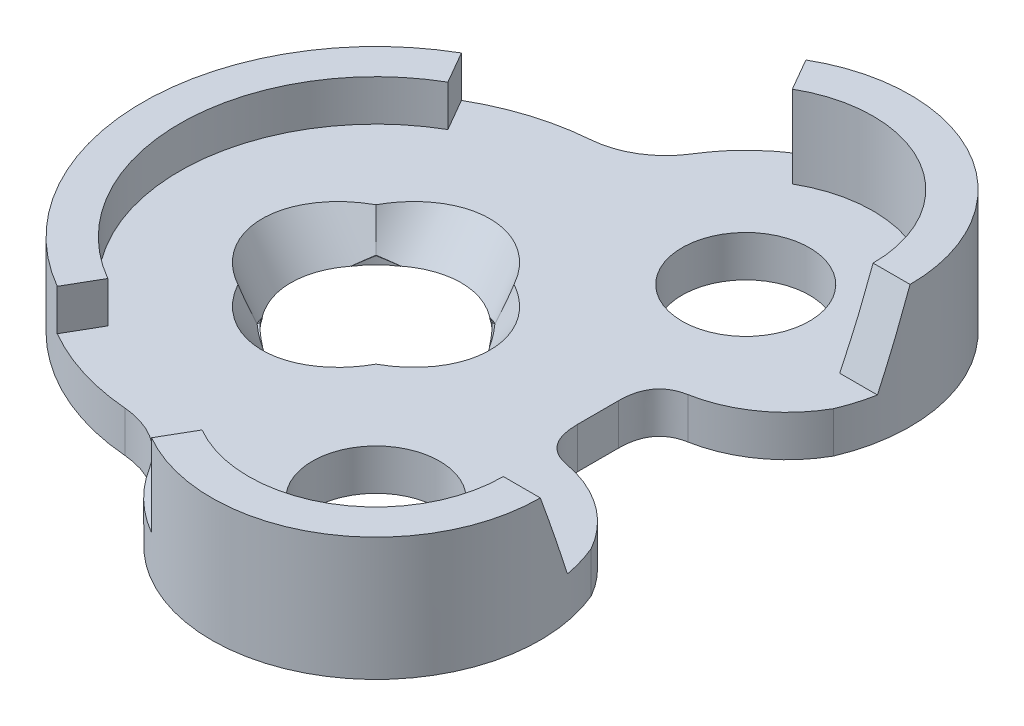
SolidWorks part; units mm, degrees
ref_plane "Front Plane" through (0, 0, 0) normal (0, 0, 1) x (1, 0, 0)
ref_plane "Top Plane" through (0, 0, 0) normal (0, 1, 0) x (1, 0, 0)
ref_plane "Right Plane" through (0, 0, 0) normal (1, 0, 0) x (0, 0, -1)
sketch "Sketch1" plane through (0, 0, 0) normal (0, 1, 0) x (1, 0, 0)
  circle A0 centre (-6.1056, 7.1668) radius 1.55
  circle A1 centre (2.8944, 7.1668) radius 1.55
  circle A3 centre (-6.1056, -1.8332) radius 1.55
  circle A4 centre (2.8944, -1.8332) radius 1.55
  arc A5 (-3.6359, 10.3133) -> (-9.2521, 4.6971) centre (-6.1056, 7.1668) ccw
  arc A6 (6.0409, 4.6971) -> (0.4247, 10.3133) centre (2.8944, 7.1668) ccw
  arc A7 (-9.2521, 0.6365) -> (-3.6359, -4.9797) centre (-6.1056, -1.8332) ccw
  arc A8 (0.224, -4.8113) -> (6.0409, 0.6365) centre (2.8944, -1.8332) ccw
  arc A9 (-9.2521, 0.6365) -> (-9.2521, 4.6971) centre (-11.4675, 2.6668) ccw
  arc A10 (-3.6359, 10.3133) -> (0.4247, 10.3133) centre (-1.6056, 12.5287) ccw
  arc A11 (6.0409, 4.6971) -> (6.0409, 0.6365) centre (8.2563, 2.6668) ccw
  arc A12 (0.224, -4.8113) -> (-3.6359, -4.9797) centre (-1.6056, -7.1951) ccw
  dimension "D3" = 7
  dimension "D5" = 6.01
  dimension "D6" = 6.01
  dimension "D11" = 6.01
  dimension "D14" = 6.01
  dimension "D17" = 4
  dimension "D18" = 4
  dimension "D19" = 4
  dimension "D20" = 4
  dimension "D21" = 3.1
  dimension "D22" = 3.1
  dimension "D23" = 3.1
  dimension "D24" = 3.1
  dimension "D1" = 9
  dimension "D2" = 9
  dimension "D4" = 7
  dimension "D7" = 7
  dimension "D8" = 7
  dimension "D9" = 7
  dimension "D10" = 7
  dimension "D12" = 7
  dimension "D13" = 7
  dimension "D15" = 9
  dimension "D16" = 0
extrude "Boss-Extrude1" add sketch "Sketch1" along normal blind 3
sketch "Sketch2" plane through (0, 3, 0) normal (0, 1, 0) x (1, 0, 0)
  arc A0 (-3.4925, 8.8346) -> (-7.7734, 4.5537) centre (-6.1056, 7.1668) ccw
  arc A1 (4.5622, 4.5537) -> (0.2812, 8.8346) centre (2.8944, 7.1668) ccw
  arc A2 (-7.7734, 0.78) -> (-3.4925, -3.501) centre (-6.1056, -1.8332) ccw
  arc A3 (0.2812, -3.501) -> (4.5622, 0.78) centre (2.8944, -1.8332) ccw
  arc A4 (0.2812, -3.501) -> (-3.4925, -3.501) centre (-1.6056, -4.0126) ccw
  arc A5 (-7.7734, 0.78) -> (-7.7734, 4.5537) centre (-8.2851, 2.6668) ccw
  arc A6 (4.5622, 4.5537) -> (4.5622, 0.78) centre (5.0738, 2.6668) ccw
  arc A7 (-3.4925, 8.8346) -> (0.2812, 8.8346) centre (-1.6056, 9.3463) ccw
  dimension "D1" = 5
  dimension "D9" = 3.91
  dimension "D10" = 3.91
  dimension "D11" = 3.91
  dimension "D12" = 3.91
  dimension "D13" = 3.1
  dimension "D14" = 3.1
  dimension "D15" = 3.1
  dimension "D16" = 3.1
  dimension "D2" = 5
  dimension "D3" = 5
  dimension "D4" = 5
  dimension "D5" = 5
  dimension "D6" = 5
  dimension "D7" = 5
  dimension "D8" = 5
extrude "Cut-Extrude1" cut sketch "Sketch2" against normal blind 2
ref_plane "Plane1" through (5.2513, 0, -2.6668) normal (1, 0, 0) x (0, 0, -1)
sketch "Sketch3" plane through (5.2513, 0, -2.6668) normal (1, 0, 0) x (0, 0, -1)
  line L1 (-2.95, 3) -> (2.95, 3)
  line L2 (-2.95, 3) -> (-2.95, 0)
  line L3 (-2.95, 0) -> (2.95, 0)
  line L4 (2.95, 3) -> (2.95, 0)
  line L5 (-8.5, 0) -> (-2.0303, 0) construction
  line L6 (-2.0303, 3) -> (-8.5, 3) construction
  dimension "D1" = 0
  dimension "D2" = 0
  dimension "D3" = 0
  dimension "D4" = 0
extrude "Boss-Extrude2" add sketch "Sketch3" along normal blind 8
sketch "Sketch4" plane through (0, 3, 0) normal (0, 1, 0) x (1, 0, 0)
  line L1 (0.4583, -1.8332) -> (14.1177, -1.8332)
  line L2 (0.4583, -1.8332) -> (0.4583, 7.1668)
  line L3 (0.4583, 7.1668) -> (14.1177, 7.1668)
  line L4 (14.1177, -1.8332) -> (14.1177, 7.1668)
  circle A0 centre (2.8944, -1.8332) radius 1.55 construction
  circle A1 centre (2.8944, 7.1668) radius 1.55 construction
  dimension "D1" = 0
  dimension "D2" = 0
extrude "Cut-Extrude2" cut sketch "Sketch4" against normal up to surface (2 mm away) draft 20
sketch "Sketch5" plane through (0, 1, 0) normal (0, 1, 0) x (1, 0, 0)
  line L11 (6.5819, -0.2832) -> (13.2513, -0.2832) construction
  circle A2 centre (10.3944, 2.7168) radius 0.75
  circle A5 centre (2.8944, 7.1668) radius 1.55 construction
  dimension "D1" = 7.5
  dimension "D2" = 3
extrude "Cut-Extrude3" cut sketch "Sketch5" against normal blind 1.3
sketch "Sketch6" plane through (0, 3, 0) normal (0, 1, 0) x (1, 0, 0)
  line L0 (-3.4925, -3.501) -> (-3.7025, -1.3276)
  line L1 (-3.7025, -1.3276) -> (0.3682, -0.9343)
  line L2 (0.3682, -0.9343) -> (0.2812, -3.501)
  arc A1 (-3.4925, -3.501) -> (0.2812, -3.501) centre (-1.6056, -4.6322) cw
extrude "Cut-Extrude4" cut sketch "Sketch6" against normal up to surface (2 mm away) up to face at (10.3944, 1, -1.9668)
sketch "Sketch9" plane through (0, 3, 0) normal (0, 1, 0) x (1, 0, 0)
  line L0 (-7.7734, 4.5537) -> (-3.2453, 5.2751)
  line L1 (-3.2453, 5.2751) -> (-4.5658, 0.235)
  line L2 (-4.5658, 0.235) -> (-7.7734, 0.78)
  arc A0 (-7.7734, 4.5537) -> (-7.7734, 0.78) centre (-8.9047, 2.6668) cw
extrude "Cut-Extrude5" cut sketch "Sketch9" against normal up to surface (2 mm away) up to face at (2.9539, 1, -2.6401)
sketch "Sketch10" plane through (0, 3, 0) normal (0, 1, 0) x (1, 0, 0)
  line L0 (-3.4925, 8.8346) -> (-4.4847, 5.0222)
  line L1 (-4.4847, 5.0222) -> (-0.858, 4.0782)
  line L2 (-0.858, 4.0782) -> (0.2812, 8.8346)
  arc A0 (-3.4925, 8.8346) -> (0.2812, 8.8346) centre (-1.6056, 9.9659) ccw
extrude "Cut-Extrude6" cut sketch "Sketch10" against normal up to surface (2 mm away) up to face at (2.9271, 1, -2.6401)
sketch "Sketch11" plane through (0, 0, 0) normal (0, -1, 0) x (1, 0, 0)
  circle A0 centre (-1.6056, -2.6668) radius 2
  circle A1 centre (-6.1056, -7.1668) radius 1.55 construction
  dimension "D3" = 4
  dimension "D1" = 4.5
  dimension "D2" = 4.5
extrude "Cut-Extrude7" cut sketch "Sketch11" against normal through all both and the other way through all
sketch "Sketch12" plane through (3.469, 4.9542, 0) normal (0.5736, 0.8192, 0) x (0.8192, -0.5736, 0)
  circle A0 centre (-1.6431, 2.6668) radius 2.025
extrude "Cut-Extrude8" cut sketch "Sketch12" against normal blind 6
pattern_circular "CirPattern1" count 4 over 360 about axis through (-1.6056, 0, -2.6668) along (0, 1, 0) of "Cut-Extrude8"
sketch "Sketch13" plane through (0, 1, 0) normal (0, 1, 0) x (1, 0, 0)
  line L1 (3.7966, 4.1643) -> (7.8944, 4.1643)
  line L2 (3.7966, 4.1643) -> (3.7966, 1.1693)
  line L3 (3.7966, 1.1693) -> (7.8944, 1.1693)
  line L4 (7.8944, 4.1643) -> (7.8944, 1.1693)
extrude "Cut-Extrude9" cut sketch "Sketch13" against normal blind 10
sketch "Sketch14" plane through (13.2513, 0, 0) normal (1, 0, 0) x (0, 0, -1)
  line L1 (-0.2832, 1) -> (5.6168, 1)
  line L2 (-0.2832, 1) -> (-0.2832, 0)
  line L3 (-0.2832, 0) -> (5.6168, 0)
  line L4 (5.6168, 1) -> (5.6168, 0)
extrude "Cut-Extrude10" cut sketch "Sketch14" against normal up to surface (0.178 mm away)
fillet "Fillet1" radius 1 4 edges at (7.8944, 0.5, -4.1643) (7.8944, 0.5, -1.1693) (3.7966, 0.5, -1.1693) (3.7966, 0.5, -4.1643)
sketch "Sketch17" plane through (0, 1, 0) normal (0, 1, 0) x (1, 0, 0)
  circle A0 centre (-6.1056, -1.8332) radius 1.6627
extrude "Boss-Extrude4" add sketch "Sketch17" against normal blind 1
sketch "Sketch16" plane through (0, 1, 0) normal (0, 1, 0) x (1, 0, 0)
  circle A0 centre (-6.1056, 7.1668) radius 1.6657
extrude "Boss-Extrude3" add sketch "Sketch16" against normal blind 1
sketch "Sketch15" plane through (0, 0, 0) normal (0, -1, 0) x (1, 0, 0)
  line L1 (6.8944, -7.1668) -> (6.8944, -13.9281)
  line L2 (6.8944, -13.9281) -> (-13.5142, -13.9281)
  line L3 (-13.5142, -13.9281) -> (-13.5142, 8.0466)
  line L4 (-13.5142, 8.0466) -> (6.8944, 8.0466)
  line L5 (6.8944, 8.0466) -> (6.8944, 1.8332)
  arc A8 (-0.5074, -9.271) -> (6.8944, -7.1668) centre (2.8944, -7.1668) ccw
  arc A9 (-0.5074, -9.271) -> (-2.0514, -8.3293) centre (-2.2083, -10.3231) ccw
  arc A10 (0.4247, -10.3133) -> (6.5819, -5.6168) centre (2.8944, -7.1668) ccw construction
  arc A12 (-2.0514, 2.9957) -> (-0.5074, 3.9374) centre (-2.2083, 4.9895) ccw
  arc A14 (-2.0514, 2.9957) -> (-2.0514, -8.3293) centre (-1.6056, -2.6668) ccw
  arc A16 (6.8944, 1.8332) -> (-0.5074, 3.9374) centre (2.8944, 1.8332) ccw
  dimension "D3" = 4
  dimension "D4" = 0
  dimension "D5" = 4
extrude "Cut-Extrude11" cut sketch "Sketch15" against normal through all both and the other way through all
sketch "Sketch18" plane through (0, 1, 0) normal (0, 1, 0) x (1, 0, 0)
  line L1 (-9.0018, 5.9593) -> (-6.4016, 5.9593)
  line L2 (-9.0018, 5.9593) -> (-9.0018, 0)
  line L3 (-9.0018, 0) -> (-6.4016, 0)
  line L4 (-6.4016, 5.9593) -> (-6.4016, 0)
extrude "Cut-Extrude12" cut sketch "Sketch18" along normal through all
sketch "Sketch19" plane through (0, 0, 0) normal (0, -1, 0) x (1, 0, 0)
  line L0 (-3.9956, -6.8064) -> (-4.4456, -7.5858)
  line L1 (-4.1056, -5.2849) -> (-4.1056, -8.0418) construction
  line L2 (-3.9956, 1.4728) -> (-4.4456, 2.2522)
  line L3 (-4.6056, 0.3332) -> (-4.6056, 3.1178) construction
  arc A0 (-3.9956, 1.4728) -> (-3.9956, -6.8064) centre (-1.6056, -2.6668) ccw
  arc A2 (-4.4456, 2.2522) -> (-4.4456, -7.5858) centre (-1.6056, -2.6668) ccw
  dimension "D1" = 150
  dimension "D2" = 150
extrude "Boss-Extrude5" add sketch "Sketch19" against normal blind 3
sketch "Sketch20" plane through (0, 1, 0) normal (0, 1, 0) x (1, 0, 0)
  line L0 (2.8944, 7.1668) -> (-0.0756, 12.311)
  line L1 (7.8944, 2.1693) -> (7.8944, 3.1643) construction
  line L2 (2.8944, -1.8332) -> (-0.182, -7.1617)
  line L4 (-0.182, -7.1617) -> (-3.2895, -7.4215)
  line L5 (-3.2895, -7.4215) -> (-3.7967, 11.5598)
  line L6 (-3.7967, 11.5598) -> (-0.0756, 12.311)
  line L7 (2.8944, -1.8332) -> (2.8944, 7.1668)
  dimension "D1" = 30
  dimension "D2" = 30
extrude "Cut-Extrude13" cut sketch "Sketch20" along normal blind 3
sketch "Sketch22" plane through (0, 3, 0) normal (0, 1, 0) x (1, 0, 0)
  line L1 (-2.1043, 10.3345) -> (-8.655, 10.3345)
  line L2 (-2.1043, 10.3345) -> (-2.1043, -5.2281)
  line L3 (-2.1043, -5.2281) -> (-8.655, -5.2281)
  line L4 (-8.655, 10.3345) -> (-8.655, -5.2281)
extrude "Cut-Extrude14" cut sketch "Sketch22" against normal blind 1
sketch "Sketch23" plane through (13.0733, 0, 0) normal (1, 0, 0) x (0, 0, -1)
  line L1 (-0.2832, 1) -> (5.6168, 1)
  line L2 (-0.2832, 1) -> (-0.2832, 0)
  line L3 (-0.2832, 0) -> (5.6168, 0)
  line L4 (5.6168, 1) -> (5.6168, 0)
extrude "Cut-Extrude15" cut sketch "Sketch23" against normal up to vertex (6.4915 mm away)
fillet "Fillet2" radius 3 2 edges at (6.5819, 0.5, -4.1643) (6.5819, 0.5, -1.1693)
